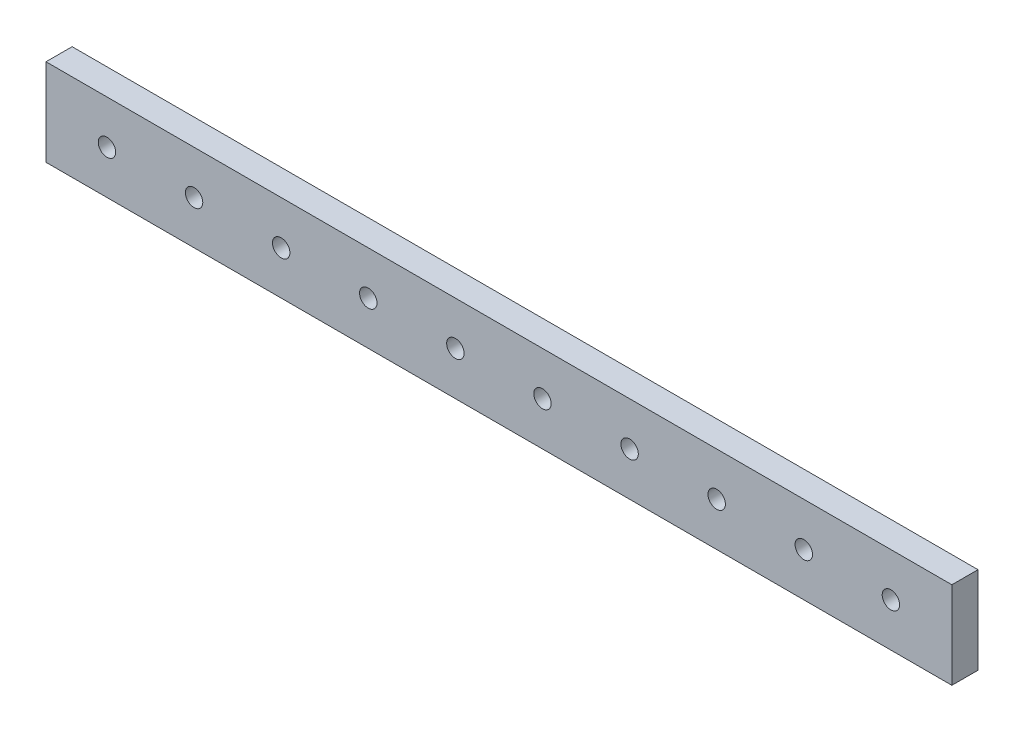
SolidWorks part; units mm, degrees
note: '?' marks a value the reader was unsure of.
material "Mahogany"
ref_plane "Front Plane" through (0, 0, 0) normal (0, 0, 1) x (1, 0, 0)
ref_plane "Top Plane" through (0, 0, 0) normal (0, 1, 0) x (1, 0, 0)
ref_plane "Right Plane" through (0, 0, 0) normal (1, 0, 0) x (0, 0, -1)
ref_axis "X-Axis" through (-88.99, 0, 0) along (1, 0, 0)?
ref_axis "Y-Axis" through (0, 55, 0) along (0, -1, 0)?
ref_axis "Z-Axis" through (0, 0, -88.99) along (0, 0, 1)?
sketch "Sketch2" plane through (0, 0, 0) normal (0, 1, 0) x (1, 0, 0)
  line L0 (171.45, 88.9) -> (-171.45, 88.9) construction
  line L1 (-165.1, 88.9) -> (165.1, 88.9)
  line L2 (-165.1, 88.9) -> (-165.1, 79.375)
  line L3 (-165.1, 79.375) -> (165.1, 79.375)
  line L4 (165.1, 88.9) -> (165.1, 79.375)
  line L5 (-161.925, 79.375) -> (161.925, 79.375) construction
extrude "Boss-Extrude1" add sketch "Sketch2" along normal up to vertex (15.875 mm away) and the other way up to vertex (15.875 mm away)
hole_wizard "1/4 (0.25) Diameter Hole1" positions "Sketch5" profile "Sketch4" hole size "1/4" standard "Ansi Inch"
sketch "Sketch5" plane through (0, 0, -79.375) normal (0, 0, 1) x (1, 0, 0)
  point P0 (-142.875, 0)
  point P4 (-111.125, 0)
  point P7 (-79.375, 0)
  point P10 (-47.625, 0)
  point P13 (-15.875, 0)
  point P16 (15.875, 0)
  point P19 (47.625, 0)
  point P22 (79.375, 0)
  point P25 (111.125, 0)
  point P28 (142.875, 0)
sketch "Sketch4" plane through (-142.875, 0, -79.375) normal (1, 0, 0) x (0, -1, 0)
  line L0 (0, 0) -> (0, 6.6702)
  line L1 (0, 6.6702) -> (3.175, 4.7625)
  line L2 (3.175, 4.7625) -> (3.175, 0)
  line L5 (3.175, 0) -> (0, 0)
  line L10 (0, 6.6702) -> (-3.175, 4.7625) construction
  line L11 (0, -6.35) -> (0, 107.95) construction
  dimension "Hole Dia." = 6.35
  dimension "Hole Depth" = 4.7625
  dimension "Drill Angle" = 118
sketch "Sketch6" [suppressed] plane through (0, 0, -101.6) normal (0, 0, 1) x (1, 0, 0)
  circle A0 centre (-142.875, 0) radius 3.175 construction
  circle A1 centre (-111.125, 0) radius 3.175 construction
  circle A2 centre (-79.375, 0) radius 3.175 construction
  circle A3 centre (-47.625, 0) radius 3.175 construction
  circle A4 centre (-15.875, 0) radius 3.175 construction
  circle A5 centre (15.875, 0) radius 3.175 construction
  circle A6 centre (47.625, 0) radius 3.175 construction
  circle A7 centre (79.375, 0) radius 3.175 construction
  circle A8 centre (111.125, 0) radius 3.175 construction
  circle A9 centre (142.875, 0) radius 3.175 construction
  circle A10 centre (-142.875, 0) radius 3.175
  circle A11 centre (-111.125, 0) radius 3.175
  circle A12 centre (-79.375, 0) radius 3.175
  circle A13 centre (-47.625, 0) radius 3.175
  circle A14 centre (-15.875, 0) radius 3.175
  circle A15 centre (15.875, 0) radius 3.175
  circle A16 centre (47.625, 0) radius 3.175
  circle A17 centre (79.375, 0) radius 3.175
  circle A18 centre (111.125, 0) radius 3.175
  circle A19 centre (142.875, 0) radius 3.175
extrude "Cut-Extrude1" [suppressed] cut sketch "Sketch6" against normal through all
